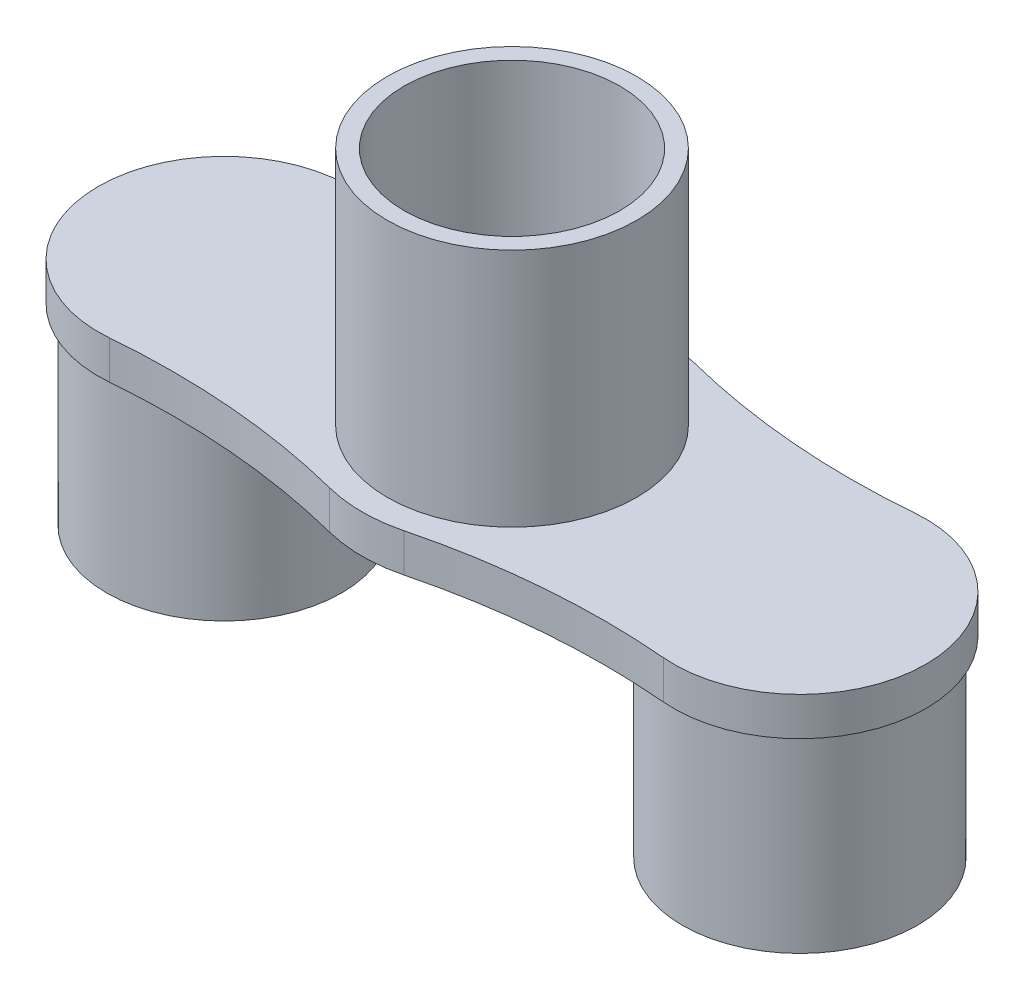
SolidWorks part; units mm, degrees
material "AISI 316 Stainless Steel Sheet (SS)"
ref_plane "Front Plane" through (0, 0, 0) normal (0, 0, 1) x (1, 0, 0)
ref_plane "Top Plane" through (0, 0, 0) normal (0, 1, 0) x (1, 0, 0)
ref_plane "Right Plane" through (0, 0, 0) normal (1, 0, 0) x (0, 0, -1)
sketch "Sketch1" plane through (0, 0, 0) normal (0, 1, 0) x (1, 0, 0)
  line L0 (0, 0) -> (0, 50000) construction
  line L1 (0, 0) -> (-50000, 0) construction
  arc A0 (-7.7407, -30.2761) -> (7.7407, -30.2761) centre (0, 0) ccw
  arc A1 (57.7504, -26.1534) -> (57.7504, 26.1534) centre (60, 0) ccw
  arc A2 (-57.7504, 26.1534) -> (-57.7504, -26.1534) centre (-60, 0) ccw
  arc A3 (-57.7504, 26.1534) -> (-7.7407, 30.2761) centre (-44.8958, 175.6016) ccw
  arc A4 (57.7504, 26.1534) -> (7.7407, 30.2761) centre (44.8958, 175.6016) cw
  arc A5 (57.7504, -26.1534) -> (7.7407, -30.2761) centre (44.8958, -175.6016) ccw
  arc A6 (-57.7504, -26.1534) -> (-7.7407, -30.2761) centre (-44.8958, -175.6016) cw
  arc A7 (7.7407, 30.2761) -> (-7.7407, 30.2761) centre (0, 0) ccw
  dimension "D1" = 62.5
  dimension "D2" = 52.5
  dimension "D5" = 150
  dimension "D3" = 60
extrude "Boss-Extrude1" add sketch "Sketch1" along normal blind 8
sketch "Sketch2" plane through (0, 8, 0) normal (0, 1, 0) x (1, 0, 0)
  circle A0 centre (0, 0) radius 22.5
  dimension "D1" = 45
extrude "Extrude-Thin1" add sketch "Sketch2" along normal blind 50 thin thin type one direction wall 3.5
sketch "Sketch3" plane through (0, 0, 0) normal (0, -1, 0) x (1, 0, 0)
  circle A0 centre (-60, 0) radius 22.5
  circle A1 centre (60, 0) radius 22.5
  dimension "D1" = 45
extrude "Extrude-Thin2" add sketch "Sketch3" along normal blind 40 thin thin type one direction wall 2
